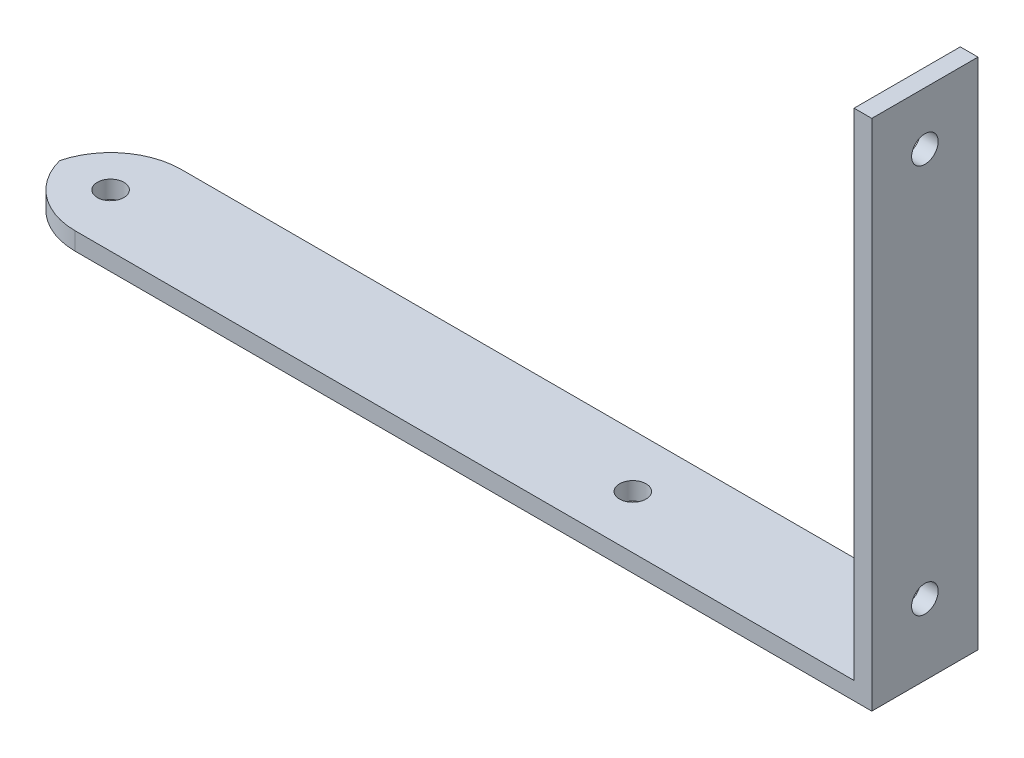
SolidWorks part; units mm, degrees
ref_plane "Front Plane" through (0, 0, 0) normal (0, 0, 1) x (1, 0, 0)
ref_plane "Top Plane" through (0, 0, 0) normal (0, 1, 0) x (1, 0, 0)
ref_plane "Right Plane" through (0, 0, 0) normal (1, 0, 0) x (0, 0, -1)
sketch "Sketch1" plane through (0, 0, 0) normal (0, 1, 0) x (1, 0, 0)
  line L1 (0, 0) -> (98, 0)
  line L2 (0, 0) -> (0, 12)
  line L3 (0, 12) -> (98, 12)
  line L4 (98, 0) -> (98, 12)
  dimension "D1" = 98
  dimension "D2" = 12
extrude "Boss-Extrude1" add sketch "Sketch1" along normal blind 2
sketch "Sketch2" plane through (0, 2, 0) normal (0, 1, 0) x (1, 0, 0)
  line L0 (98, 12) -> (0, 12) construction
  line L1 (98, 0) -> (96, 0)
  line L2 (98, 0) -> (98, 12)
  line L3 (98, 12) -> (96, 12)
  line L4 (96, 0) -> (96, 12)
  dimension "D1" = 2
extrude "Boss-Extrude2" add sketch "Sketch2" along normal blind 56
sketch "Sketch3" plane through (0, 2, 0) normal (0, 1, 0) x (1, 0, 0)
  line L0 (0, 12) -> (0, 0) construction
  line L1 (0, 0) -> (96, 0) construction
  circle A0 centre (6, 6) radius 1.5
  circle A1 centre (65, 6) radius 1.5
  dimension "D1" = 3
  dimension "D2" = 6
  dimension "D3" = 6
  dimension "D4" = 59
extrude "Cut-Extrude1" cut sketch "Sketch3" against normal through all
fillet "Fillet1" radius 8 2 edges at (0, 1, 0) (0, 1, -12)
sketch "Sketch4" plane through (96, 0, 0) normal (-1, 0, 0) x (0, 0, 1)
  line L1 (-12, 2) -> (0, 2) construction
  line L2 (-12, 58) -> (0, 58) construction
  circle A0 centre (-6, 8) radius 1.5
  circle A2 centre (-6, 52) radius 1.5
  point P10 (-6, 58)
  dimension "D3" = 6
  dimension "D5" = 6
extrude "Cut-Extrude2" cut sketch "Sketch4" against normal through all
